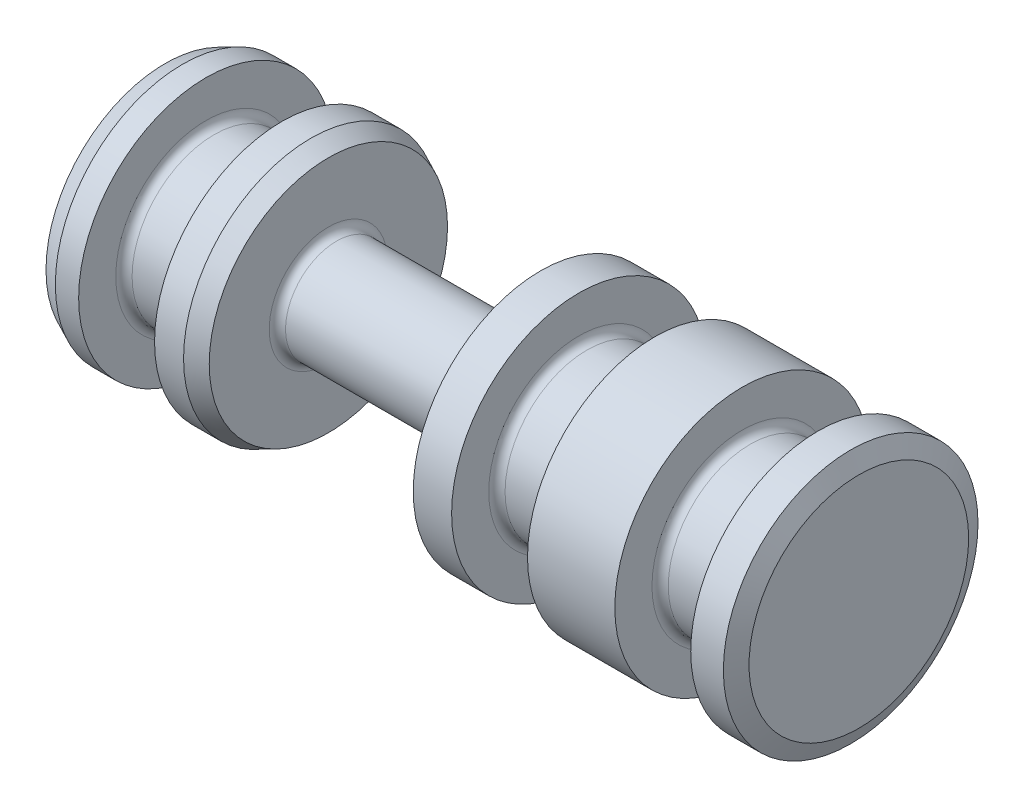
SolidWorks part; units mm, degrees
ref_plane "Front Plane" through (0, 0, 0) normal (0, 0, 1) x (1, 0, 0)
ref_plane "Top Plane" through (0, 0, 0) normal (0, 1, 0) x (1, 0, 0)
ref_plane "Right Plane" through (0, 0, 0) normal (1, 0, 0) x (0, 0, -1)
sketch "Sketch1" plane through (0, 0, 0) normal (1, 0, 0) x (0, 0, -1)
  circle A0 centre (0, 0) radius 3.9624
  dimension "D1" = 7.9248
extrude "Boss-Extrude1" add sketch "Sketch1" along normal blind 21.59
sketch "Sketch2" plane through (0, 0, 0) normal (0, 0, 1) x (1, 0, 0)
  line L0 (-1.6174, 0) -> (23.3579, 0) construction
  line L1 (1.27, 3.9624) -> (3.6322, 3.9624)
  line L2 (3.6322, 3.9624) -> (3.6322, 2.5527)
  line L3 (3.6322, 2.5527) -> (1.27, 2.5527)
  line L4 (1.27, 2.5527) -> (1.27, 3.9624)
  line L5 (0, 3.9624) -> (0, -3.9624) construction
  line L6 (16.51, 5.6982) -> (16.51, -5.5364) construction
  line L7 (21.59, -3.9624) -> (21.59, 3.9624) construction
  line L8 (17.9578, 3.9624) -> (20.32, 3.9624)
  line L9 (20.32, 3.9624) -> (20.32, 2.5527)
  line L10 (20.32, 2.5527) -> (17.9578, 2.5527)
  line L11 (17.9578, 2.5527) -> (17.9578, 3.9624)
  line L12 (12.8778, 3.9624) -> (15.24, 3.9624)
  line L13 (15.24, 3.9624) -> (15.24, 2.5527)
  line L14 (15.24, 2.5527) -> (12.8778, 2.5527)
  line L15 (12.8778, 2.5527) -> (12.8778, 3.9624)
  line L17 (5.08, 3.9624) -> (11.43, 3.9624)
  line L18 (5.08, 3.9624) -> (5.08, 1.5875)
  line L19 (5.08, 1.5875) -> (11.43, 1.5875)
  line L20 (11.43, 3.9624) -> (11.43, 1.5875)
  dimension "D1" = 7.9248
  dimension "D2" = 5.1054
  dimension "D3" = 2.3622
  dimension "D4" = 1.27
  dimension "D5" = 5.08
  dimension "D6" = 1.27
  dimension "D7" = 6.35
  dimension "D8" = 5.08
  dimension "D9" = 10.16
  dimension "D10" = 3.175
revolve "Cut-Revolve1" cut sketch "Sketch2" angle 360 about L0
fillet "Fillet1" radius 0.254 8 edges at (20.32, 0, 2.5527) (17.9578, 0, 2.5527) (15.24, 0, 2.5527) (12.8778, 0, 2.5527) (11.43, 0, 1.5875) (5.08, 0, 1.5875) (3.6322, 0, 2.5527) (1.27, 0, 2.5527)
chamfer "Chamfer1" distance 0.254 angle 65 4 edges at (21.59, 0, -3.9624) (11.43, 0, 3.9624) (5.08, 0, 3.9624) (0, 0, -3.9624) first distance on face at (21.59, 0, -3.9624) first distance on face at (11.43, 0, 3.9624) first distance on face at (5.08, 0, -1.8415) first distance on face at (0, 0, -3.9624)
